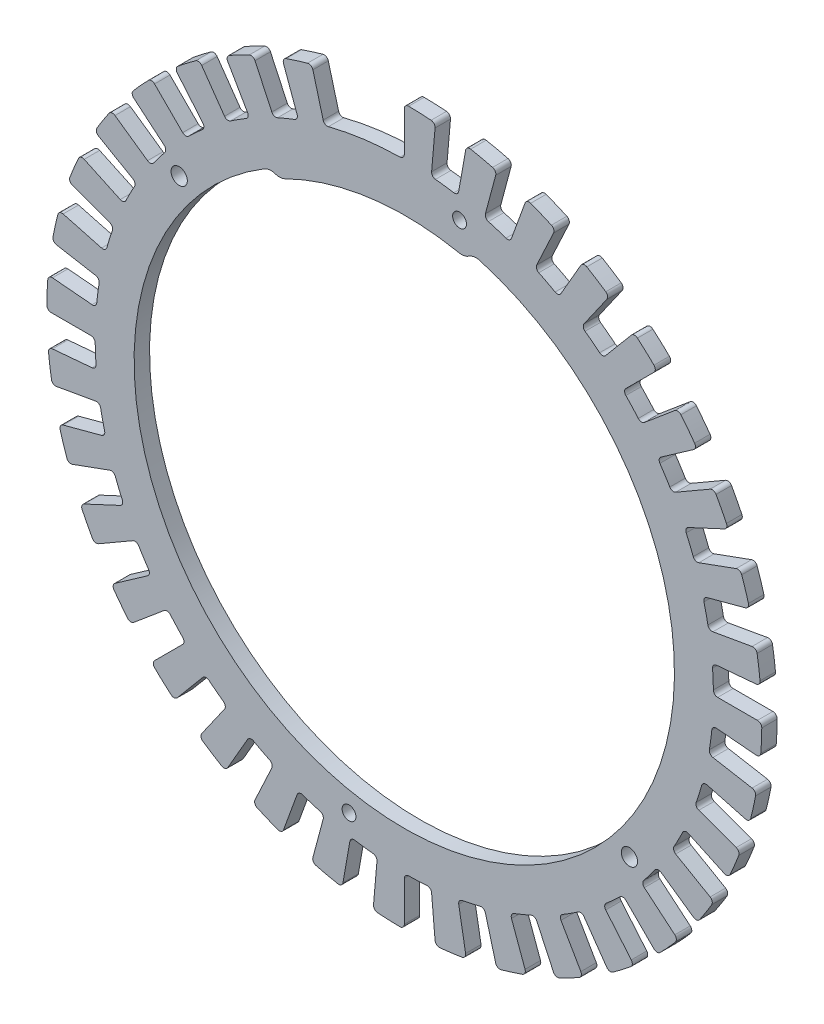
SolidWorks part; units mm, degrees
ref_plane "Front Plane" through (0, 0, 0) normal (0, 0, 1) x (1, 0, 0)
ref_plane "Top Plane" through (0, 0, 0) normal (0, 1, 0) x (1, 0, 0)
ref_plane "Right Plane" through (0, 0, 0) normal (1, 0, 0) x (0, 0, -1)
sketch "Sketch1" plane through (0, 0, 0) normal (0, 0, 1) x (1, 0, 0)
  line L0 (0, 82.7) -> (0, 71.5) construction
  line L1 (7.2078, 82.3853) -> (6.2316, 71.2279) construction
  line L2 (0, 71.5) -> (0, 0) construction
  line L3 (6.2316, 71.2279) -> (0, 0) construction
  line L4 (12.5883, 71.3918) -> (14.186, 80.4528) construction
  line L5 (12.5883, 71.3918) -> (0, 0) construction
  line L8 (0, 0) -> (12.7842, 65.769) construction
  line L12 (13.6428, 70.1863) -> (12.7842, 65.769) construction
  line L15 (12.7842, 65.769) -> (11.9256, 61.3517) construction
  line L18 (7.3144, 72.1301) -> (6.3182, 72.2172) construction
  line L21 (7.3144, 72.1301) -> (7.2135, 71.1352) construction
  line L24 (12.5883, 71.3918) -> (11.6035, 71.5654) construction
  line L27 (11.6035, 71.5654) -> (11.4434, 70.5783) construction
  line L30 (1.0122, 82.6938) -> (1, 81.6939) construction
  line L33 (1, 81.6939) -> (0, 81.6939) construction
  line L36 (7.1201, 81.383) -> (6.1239, 81.4702) construction
  line L39 (6.1239, 81.4702) -> (6.1989, 82.4674) construction
  line L42 (7.1201, 81.383) -> (6.3182, 72.2172)
  line L45 (0, 81.6939) -> (0, 72.4931)
  line L48 (0, 72.4931) -> (-1, 72.4931) construction
  line L51 (-1, 72.4931) -> (-0.9862, 71.4932) construction
  line L109 (0, -82.7) -> (0, -71.5) [skipped]
  line L111 (14.3607, 81.4436) -> (12.4158, 70.4138) [skipped]
  line L115 (41.35, 71.6203) -> (35.75, 61.9208) [skipped]
  line L117 (53.1585, 63.3519) -> (45.9593, 54.7722) [skipped]
  line L118 (-63.3519, -53.1585) -> (-54.7722, -45.9593) [skipped]
  line L119 (63.3519, 53.1585) -> (54.7722, 45.9593) [skipped]
  line L121 (71.6203, 41.35) -> (61.9208, 35.75) [skipped]
  line L123 (77.7126, 28.2851) -> (67.188, 24.4544) [skipped]
  line L125 (81.4436, 14.3607) -> (70.4138, 12.4158) [skipped]
  line L127 (82.7, 0) -> (71.5, 0) [skipped]
  line L129 (81.4436, -14.3607) -> (70.4138, -12.4158) [skipped]
  line L131 (77.7126, -28.2851) -> (67.188, -24.4544) [skipped]
  line L133 (71.6203, -41.35) -> (61.9208, -35.75) [skipped]
  line L135 (63.3519, -53.1585) -> (54.7722, -45.9593) [skipped]
  line L137 (53.1585, -63.3519) -> (45.9593, -54.7722) [skipped]
  line L139 (41.35, -71.6203) -> (35.75, -61.9208) [skipped]
  line L141 (28.2851, -77.7126) -> (24.4544, -67.188) [skipped]
  line L142 (14.3607, -81.4436) -> (12.4158, -70.4138) [skipped]
  line L143 (34.9505, 74.9517) -> (30.2172, 64.801) [skipped]
  line L144 (47.4348, 67.7439) -> (41.0107, 58.5694) [skipped]
  line L145 (58.4777, 58.4777) -> (50.5581, 50.5581) [skipped]
  line L146 (67.7439, 47.4348) -> (58.5694, 41.0107) [skipped]
  line L147 (74.9517, 34.9505) -> (64.801, 30.2172) [skipped]
  line L148 (79.8821, 21.4043) -> (69.0637, 18.5056) [skipped]
  line L149 (82.3853, 7.2078) -> (71.2279, 6.2316) [skipped]
  line L150 (82.3853, -7.2078) -> (71.2279, -6.2316) [skipped]
  line L151 (79.8821, -21.4043) -> (69.0637, -18.5056) [skipped]
  line L152 (74.9517, -34.9505) -> (64.801, -30.2172) [skipped]
  line L153 (67.7439, -47.4348) -> (58.5694, -41.0107) [skipped]
  line L154 (58.4777, -58.4777) -> (50.5581, -50.5581) [skipped]
  line L155 (47.4348, -67.7439) -> (41.0107, -58.5694) [skipped]
  line L156 (34.9505, -74.9517) -> (30.2172, -64.801) [skipped]
  line L157 (21.4043, -79.8821) -> (18.5056, -69.0637) [skipped]
  line L158 (7.2078, -82.3853) -> (6.2316, -71.2279) [skipped]
  line L159 (-7.2078, -82.3853) -> (-6.2316, -71.2279) [skipped]
  line L160 (-21.4043, -79.8821) -> (-18.5056, -69.0637) [skipped]
  line L161 (-34.9505, -74.9517) -> (-30.2172, -64.801) [skipped]
  line L162 (-47.4348, -67.7439) -> (-41.0107, -58.5694) [skipped]
  line L163 (-58.4777, -58.4777) -> (-50.5581, -50.5581) [skipped]
  line L164 (-67.7439, -47.4348) -> (-58.5694, -41.0107) [skipped]
  line L165 (-74.9517, -34.9505) -> (-64.801, -30.2172) [skipped]
  line L166 (-79.8821, -21.4043) -> (-69.0637, -18.5056) [skipped]
  line L167 (-82.3853, -7.2078) -> (-71.2279, -6.2316) [skipped]
  line L168 (-82.3853, 7.2078) -> (-71.2279, 6.2316) [skipped]
  line L169 (-79.8821, 21.4043) -> (-69.0637, 18.5056) [skipped]
  line L170 (-74.9517, 34.9505) -> (-64.801, 30.2172) [skipped]
  line L171 (-67.7439, 47.4348) -> (-58.5694, 41.0107) [skipped]
  line L172 (-58.4777, 58.4777) -> (-50.5581, 50.5581) [skipped]
  line L173 (-47.4348, 67.7439) -> (-41.0107, 58.5694) [skipped]
  line L174 (-34.9505, 74.9517) -> (-30.2172, 64.801) [skipped]
  line L175 (-21.4043, 79.8821) -> (-18.5056, 69.0637) [skipped]
  line L176 (21.4043, 79.8821) -> (18.5056, 69.0637) [skipped]
  line L209 (0, 0) -> (-12.7842, -65.769) construction
  line L210 (0, 0) -> (-52.0688, 42.1645) construction
  line L211 (0, 0) -> (52.0688, -42.1645) construction
  line L212 (14.186, 80.4528) -> (12.5883, 71.3918)
  line L213 (21.1439, 78.9102) -> (18.7626, 70.023)
  line L214 (27.941, 76.7671) -> (24.7941, 68.1212)
  line L215 (34.5253, 74.0398) -> (30.6369, 65.7011)
  line L216 (40.8469, 70.749) -> (36.2466, 62.7809)
  line L217 (46.8577, 66.9197) -> (41.5803, 59.3829)
  line L218 (52.5118, 62.5811) -> (46.5977, 55.5329)
  line L219 (57.7663, 57.7663) -> (51.2604, 51.2604)
  line L220 (62.5811, 52.5118) -> (55.5329, 46.5977)
  line L221 (66.9197, 46.8577) -> (59.3829, 41.5803)
  line L222 (70.749, 40.8469) -> (62.7809, 36.2466)
  line L223 (74.0398, 34.5253) -> (65.7011, 30.6369)
  line L224 (76.7671, 27.941) -> (68.1212, 24.7941)
  line L225 (78.9102, 21.1439) -> (70.023, 18.7626)
  line L226 (80.4528, 14.186) -> (71.3918, 12.5883)
  line L227 (81.383, 7.1201) -> (72.2172, 6.3182)
  line L228 (81.6939, 0) -> (72.4931, 0)
  line L229 (81.383, -7.1201) -> (72.2172, -6.3182)
  line L230 (80.4528, -14.186) -> (71.3918, -12.5883)
  line L231 (78.9102, -21.1439) -> (70.023, -18.7626)
  line L232 (76.7671, -27.941) -> (68.1212, -24.7941)
  line L233 (74.0398, -34.5253) -> (65.7011, -30.6369)
  line L234 (70.749, -40.8469) -> (62.7809, -36.2466)
  line L235 (66.9197, -46.8577) -> (59.3829, -41.5803)
  line L236 (62.5811, -52.5118) -> (55.5329, -46.5977)
  line L237 (57.7663, -57.7663) -> (51.2604, -51.2604)
  line L238 (52.5118, -62.5811) -> (46.5977, -55.5329)
  line L239 (46.8577, -66.9197) -> (41.5803, -59.3829)
  line L240 (40.8469, -70.749) -> (36.2466, -62.7809)
  line L241 (34.5253, -74.0398) -> (30.6369, -65.7011)
  line L242 (27.941, -76.7671) -> (24.7941, -68.1212)
  line L243 (21.1439, -78.9102) -> (18.7626, -70.023)
  line L244 (14.186, -80.4528) -> (12.5883, -71.3918)
  line L245 (7.1201, -81.383) -> (6.3182, -72.2172)
  line L246 (0, -81.6939) -> (0, -72.4931)
  line L247 (-7.1201, -81.383) -> (-6.3182, -72.2172)
  line L248 (-14.186, -80.4528) -> (-12.5883, -71.3918)
  line L249 (-21.1439, -78.9102) -> (-18.7626, -70.023)
  line L250 (-27.941, -76.7671) -> (-24.7941, -68.1212)
  line L251 (-34.5253, -74.0398) -> (-30.6369, -65.7011)
  line L252 (-40.8469, -70.749) -> (-36.2466, -62.7809)
  line L253 (-46.8577, -66.9197) -> (-41.5803, -59.3829)
  line L254 (-52.5118, -62.5811) -> (-46.5977, -55.5329)
  line L255 (-57.7663, -57.7663) -> (-51.2604, -51.2604)
  line L256 (-62.5811, -52.5118) -> (-55.5329, -46.5977)
  line L257 (-66.9197, -46.8577) -> (-59.3829, -41.5803)
  line L258 (-70.749, -40.8469) -> (-62.7809, -36.2466)
  line L259 (-74.0398, -34.5253) -> (-65.7011, -30.6369)
  line L260 (-76.7671, -27.941) -> (-68.1212, -24.7941)
  line L261 (-78.9102, -21.1439) -> (-70.023, -18.7626)
  line L262 (-80.4528, -14.186) -> (-71.3918, -12.5883)
  line L263 (-81.383, -7.1201) -> (-72.2172, -6.3182)
  line L264 (-81.6939, 0) -> (-72.4931, 0)
  line L265 (-81.383, 7.1201) -> (-72.2172, 6.3182)
  line L266 (-80.4528, 14.186) -> (-71.3918, 12.5883)
  line L267 (-78.9102, 21.1439) -> (-70.023, 18.7626)
  line L268 (-76.7671, 27.941) -> (-68.1212, 24.7941)
  line L269 (-74.0398, 34.5253) -> (-65.7011, 30.6369)
  line L270 (-70.749, 40.8469) -> (-62.7809, 36.2466)
  line L271 (-66.9197, 46.8577) -> (-59.3829, 41.5803)
  line L272 (-62.5811, 52.5118) -> (-55.5329, 46.5977)
  line L273 (-57.7663, 57.7663) -> (-51.2604, 51.2604)
  line L274 (-52.5118, 62.5811) -> (-46.5977, 55.5329)
  line L275 (-46.8577, 66.9197) -> (-41.5803, 59.3829)
  line L276 (-40.8469, 70.749) -> (-36.2466, 62.7809)
  line L277 (-34.5253, 74.0398) -> (-30.6369, 65.7011)
  line L278 (-27.941, 76.7671) -> (-24.7941, 68.1212)
  line L279 (-21.1439, 78.9102) -> (-18.7626, 70.023)
  line L280 (-0.9864, 71.4932) -> (-0.9862, 71.4932)
  line L281 (-32.3995, 53.4464) -> (-30.8444, 50.881) construction
  line L282 (-30.8444, 50.881) -> (-29.8635, 53.7161) construction
  line L283 (-29.8635, 53.7161) -> (-28.8826, 56.5512) construction
  line L284 (-28.8826, 56.5512) -> (-27.5181, 53.8795) construction
  line L285 (17.4626, 60.0109) -> (16.6244, 57.1304) construction
  line L286 (16.6244, 57.1304) -> (14.9432, 59.615) construction
  line L289 (13.262, 62.0997) -> (14.9432, 59.615) construction
  line L290 (-7.4414, 56.5227) -> (0, 0) construction
  line L291 (-27.5181, 53.8795) -> (-7.4414, 56.5227) construction
  line L292 (-7.4414, 56.5227) -> (12.6354, 59.1658) construction
  line L293 (13.262, 62.0997) -> (12.6354, 59.1658) construction
  line L294 (-28.4278, 55.6607) -> (13.0531, 61.1217) construction
  circle A0 centre (0, 0) radius 82.7 construction
  arc A1 (-32.3995, 53.4464) -> (17.4626, 60.0109) centre (0, 0) ccw
  circle A73 centre (12.7842, 65.769) radius 1.6
  circle A74 centre (12.7842, 65.769) radius 2.1 construction
  arc A78 (0, 71.5) -> (6.2316, 71.2279) centre (0, 0) cw construction
  arc A79 (6.3182, 72.2172) -> (7.2135, 71.1352) centre (7.3144, 72.1301) ccw
  arc A80 (11.4434, 70.5783) -> (12.5883, 71.3918) centre (11.6035, 71.5654) ccw construction
  arc A81 (7.1201, 81.383) -> (6.1989, 82.4674) centre (6.1239, 81.4702) ccw
  arc A82 (0, 81.6939) -> (1.0122, 82.6938) centre (1, 81.6939) cw
  arc A83 (6.5367, 74.7146) -> (13.0236, 73.8606) centre (0, 0) cw [skipped]
  arc A84 (7.2135, 71.1352) -> (11.4434, 70.5783) centre (0, 0) cw
  arc A85 (0, 82.7) -> (7.2078, 82.3853) centre (0, 0) cw [skipped]
  arc A86 (1.0122, 82.6938) -> (6.1989, 82.4674) centre (0, 0) cw
  arc A87 (28.2851, 77.7126) -> (34.9505, 74.9517) centre (0, 0) cw [skipped]
  arc A88 (31.6964, 67.9731) -> (37.5, 64.9519) centre (0, 0) cw [skipped]
  arc A89 (41.35, 71.6203) -> (47.4348, 67.7439) centre (0, 0) cw [skipped]
  arc A90 (43.0182, 61.4364) -> (48.2091, 57.4533) centre (0, 0) cw [skipped]
  arc A91 (53.1585, 63.3519) -> (58.4777, 58.4777) centre (0, 0) cw [skipped]
  arc A92 (53.033, 53.033) -> (57.4533, 48.2091) centre (0, 0) cw [skipped]
  arc A93 (63.3519, 53.1585) -> (67.7439, 47.4348) centre (0, 0) cw [skipped]
  arc A94 (61.4364, 43.0182) -> (64.9519, 37.5) centre (0, 0) cw [skipped]
  arc A95 (71.6203, 41.35) -> (74.9517, 34.9505) centre (0, 0) cw [skipped]
  arc A96 (67.9731, 31.6964) -> (70.4769, 25.6515) centre (0, 0) cw [skipped]
  arc A97 (77.7126, 28.2851) -> (79.8821, 21.4043) centre (0, 0) cw [skipped]
  arc A98 (72.4444, 19.4114) -> (73.8606, 13.0236) centre (0, 0) cw [skipped]
  arc A99 (81.4436, 14.3607) -> (82.3853, 7.2078) centre (0, 0) cw [skipped]
  arc A100 (74.7146, 6.5367) -> (75, 0) centre (0, 0) cw [skipped]
  arc A101 (82.7, 0) -> (82.3853, -7.2078) centre (0, 0) cw [skipped]
  arc A102 (74.7146, -6.5367) -> (73.8606, -13.0236) centre (0, 0) cw [skipped]
  arc A103 (81.4436, -14.3607) -> (79.8821, -21.4043) centre (0, 0) cw [skipped]
  arc A104 (72.4444, -19.4114) -> (70.4769, -25.6515) centre (0, 0) cw [skipped]
  arc A105 (77.7126, -28.2851) -> (74.9517, -34.9505) centre (0, 0) cw [skipped]
  arc A106 (67.9731, -31.6964) -> (64.9519, -37.5) centre (0, 0) cw [skipped]
  arc A107 (71.6203, -41.35) -> (67.7439, -47.4348) centre (0, 0) cw [skipped]
  arc A108 (61.4364, -43.0182) -> (57.4533, -48.2091) centre (0, 0) cw [skipped]
  arc A109 (63.3519, -53.1585) -> (58.4777, -58.4777) centre (0, 0) cw [skipped]
  arc A110 (53.033, -53.033) -> (48.2091, -57.4533) centre (0, 0) cw [skipped]
  arc A111 (53.1585, -63.3519) -> (47.4348, -67.7439) centre (0, 0) cw [skipped]
  arc A112 (43.0182, -61.4364) -> (37.5, -64.9519) centre (0, 0) cw [skipped]
  arc A113 (41.35, -71.6203) -> (34.9505, -74.9517) centre (0, 0) cw [skipped]
  arc A114 (31.6964, -67.9731) -> (25.6515, -70.4769) centre (0, 0) cw [skipped]
  arc A115 (28.2851, -77.7126) -> (21.4043, -79.8821) centre (0, 0) cw [skipped]
  arc A116 (19.4114, -72.4444) -> (13.0236, -73.8606) centre (0, 0) cw [skipped]
  arc A117 (14.3607, -81.4436) -> (7.2078, -82.3853) centre (0, 0) cw [skipped]
  arc A118 (6.5367, -74.7146) -> (0, -75) centre (0, 0) cw [skipped]
  arc A119 (0, -82.7) -> (-7.2078, -82.3853) centre (0, 0) cw [skipped]
  arc A120 (-6.5367, -74.7146) -> (-13.0236, -73.8606) centre (0, 0) cw [skipped]
  arc A121 (-14.3607, -81.4436) -> (-21.4043, -79.8821) centre (0, 0) cw [skipped]
  arc A122 (-28.2851, -77.7126) -> (-34.9505, -74.9517) centre (0, 0) cw [skipped]
  arc A123 (-19.4114, -72.4444) -> (-25.6515, -70.4769) centre (0, 0) cw [skipped]
  arc A124 (-31.6964, -67.9731) -> (-37.5, -64.9519) centre (0, 0) cw [skipped]
  arc A125 (-41.35, -71.6203) -> (-47.4348, -67.7439) centre (0, 0) cw [skipped]
  arc A126 (-43.0182, -61.4364) -> (-48.2091, -57.4533) centre (0, 0) cw [skipped]
  arc A127 (-53.1585, -63.3519) -> (-58.4777, -58.4777) centre (0, 0) cw [skipped]
  arc A128 (-53.033, -53.033) -> (-57.4533, -48.2091) centre (0, 0) cw [skipped]
  arc A129 (-63.3519, -53.1585) -> (-67.7439, -47.4348) centre (0, 0) cw [skipped]
  arc A130 (-61.4364, -43.0182) -> (-64.9519, -37.5) centre (0, 0) cw [skipped]
  arc A131 (-71.6203, -41.35) -> (-74.9517, -34.9505) centre (0, 0) cw [skipped]
  arc A132 (-67.9731, -31.6964) -> (-70.4769, -25.6515) centre (0, 0) cw [skipped]
  arc A133 (-77.7126, -28.2851) -> (-79.8821, -21.4043) centre (0, 0) cw [skipped]
  arc A134 (-72.4444, -19.4114) -> (-73.8606, -13.0236) centre (0, 0) cw [skipped]
  arc A135 (-81.4436, -14.3607) -> (-82.3853, -7.2078) centre (0, 0) cw [skipped]
  arc A136 (-74.7146, -6.5367) -> (-75, 0) centre (0, 0) cw [skipped]
  arc A137 (-82.7, 0) -> (-82.3853, 7.2078) centre (0, 0) cw [skipped]
  arc A138 (-74.7146, 6.5367) -> (-73.8606, 13.0236) centre (0, 0) cw [skipped]
  arc A139 (-81.4436, 14.3607) -> (-79.8821, 21.4043) centre (0, 0) cw [skipped]
  arc A140 (-72.4444, 19.4114) -> (-70.4769, 25.6515) centre (0, 0) cw [skipped]
  arc A141 (-77.7126, 28.2851) -> (-74.9517, 34.9505) centre (0, 0) cw [skipped]
  arc A142 (-67.9731, 31.6964) -> (-64.9519, 37.5) centre (0, 0) cw [skipped]
  arc A143 (-71.6203, 41.35) -> (-67.7439, 47.4348) centre (0, 0) cw [skipped]
  arc A144 (-61.4364, 43.0182) -> (-57.4533, 48.2091) centre (0, 0) cw [skipped]
  arc A145 (-63.3519, 53.1585) -> (-58.4777, 58.4777) centre (0, 0) cw [skipped]
  arc A146 (-53.033, 53.033) -> (-48.2091, 57.4533) centre (0, 0) cw [skipped]
  arc A147 (-53.1585, 63.3519) -> (-47.4348, 67.7439) centre (0, 0) cw [skipped]
  arc A148 (-43.0182, 61.4364) -> (-37.5, 64.9519) centre (0, 0) cw [skipped]
  arc A149 (-41.35, 71.6203) -> (-34.9505, 74.9517) centre (0, 0) cw [skipped]
  arc A150 (-31.6964, 67.9731) -> (-25.6515, 70.4769) centre (0, 0) cw [skipped]
  arc A151 (-28.2851, 77.7126) -> (-21.4043, 79.8821) centre (0, 0) cw [skipped]
  arc A152 (-19.4114, 72.4444) -> (-13.0236, 73.8606) centre (0, 0) cw [skipped]
  arc A153 (14.3607, 81.4436) -> (21.4043, 79.8821) centre (0, 0) cw [skipped]
  arc A154 (19.4114, 72.4444) -> (25.6515, 70.4769) centre (0, 0) cw [skipped]
  arc A155 (0, 72.4931) -> (-0.9862, 71.4932) centre (-1, 72.4931) cw
  circle A367 centre (-12.7842, -65.769) radius 1.6
  circle A368 centre (52.0688, -42.1645) radius 1.8812
  circle A369 centre (-52.0688, 42.1645) radius 1.8812
  circle A370 centre (0, 0) radius 71.5 construction
  arc A371 (12.5883, 71.3918) -> (11.4434, 70.5783) centre (11.6035, 71.5654) cw
  arc A372 (14.186, 80.4528) -> (15.3565, 81.2617) centre (15.1708, 80.2791) cw
  arc A373 (15.3565, 81.2617) -> (20.425, 80.1381) centre (0, 0) cw
  arc A374 (21.1439, 78.9102) -> (20.425, 80.1381) centre (20.178, 79.169) ccw
  arc A375 (18.7626, 70.023) -> (19.4564, 68.8019) centre (19.7285, 69.7641) ccw
  arc A376 (19.4564, 68.8019) -> (23.5254, 67.5189) centre (0, 0) cw
  arc A377 (24.7941, 68.1212) -> (23.5254, 67.5189) centre (23.8544, 68.4633) cw
  arc A378 (27.941, 76.7671) -> (29.2341, 77.3606) centre (28.8806, 76.4251) cw
  arc A379 (29.2341, 77.3606) -> (34.0305, 75.3738) centre (0, 0) cw
  arc A380 (34.5253, 74.0398) -> (34.0305, 75.3738) centre (33.619, 74.4624) ccw
  arc A381 (30.6369, 65.7011) -> (31.1081, 64.3781) centre (31.5432, 65.2784) ccw
  arc A382 (31.1081, 64.3781) -> (34.8925, 62.408) centre (0, 0) cw
  arc A384 (36.2466, 62.7809) -> (34.8925, 62.408) centre (35.3805, 63.2809) cw
  arc A385 (40.8469, 70.749) -> (42.2235, 71.1088) centre (41.713, 70.249) cw
  arc A386 (42.2235, 71.1088) -> (46.602, 68.3194) centre (0, 0) cw
  arc A387 (46.8577, 66.9197) -> (46.602, 68.3194) centre (46.0385, 67.4933) ccw
  arc A388 (41.5803, 59.3829) -> (41.8147, 57.9981) centre (42.3995, 58.8093) ccw
  arc A389 (41.8147, 57.9981) -> (45.1995, 55.4009) centre (0, 0) cw
  arc A390 (46.5977, 55.5329) -> (45.1995, 55.4009) centre (45.8316, 56.1757) cw
  arc A391 (52.5118, 62.5811) -> (53.93, 62.6965) centre (53.2779, 61.9384) cw
  arc A392 (53.93, 62.6965) -> (57.7576, 59.1891) centre (0, 0) cw
  arc A393 (57.7663, 57.7663) -> (57.7576, 59.1891) centre (57.0592, 58.4734) ccw
  arc A394 (51.2604, 51.2604) -> (51.2507, 49.856) centre (51.9675, 50.5533) ccw
  arc A395 (51.2507, 49.856) -> (54.133, 46.7104) centre (0, 0) cw
  arc A396 (55.5329, 46.5977) -> (54.133, 46.7104) centre (54.8902, 47.3637) cw
  arc A397 (62.5811, 52.5118) -> (63.9978, 52.3791) centre (63.2239, 51.7458) cw
  arc A398 (63.9978, 52.3791) -> (67.1582, 48.2604) centre (0, 0) cw
  arc A399 (66.9197, 46.8577) -> (67.1582, 48.2604) centre (66.3461, 47.6768) ccw
  arc A400 (59.3829, 41.5803) -> (59.1295, 40.199) centre (59.9565, 40.7612) ccw
  arc A401 (59.1295, 40.199) -> (61.4218, 36.6007) centre (0, 0) cw
  arc A402 (62.7809, 36.2466) -> (61.4218, 36.6007) centre (62.2809, 37.1126) cw
  arc A403 (70.749, 40.8469) -> (72.1211, 40.4703) centre (71.249, 39.9809) cw
  arc A404 (72.1211, 40.4703) -> (74.5182, 35.8653) centre (0, 0) cw
  arc A405 (74.0398, 34.5253) -> (74.5182, 35.8653) centre (73.6172, 35.4316) ccw
  arc A406 (65.7011, 30.6369) -> (65.2116, 29.3205) centre (66.1237, 29.7306) ccw
  arc A407 (65.2116, 29.3205) -> (66.8443, 25.3788) centre (0, 0) cw
  arc A408 (68.1212, 24.7941) -> (66.8443, 25.3788) centre (67.7792, 25.7338) cw
  arc A409 (76.7671, 27.941) -> (78.053, 27.3318) centre (77.1092, 27.0013) cw
  arc A410 (78.053, 27.3318) -> (79.6141, 22.3805) centre (0, 0) cw
  arc A411 (78.9102, 21.1439) -> (79.6141, 22.3805) centre (78.6514, 22.1099) ccw
  arc A412 (70.023, 18.7626) -> (69.3124, 17.5512) centre (70.2818, 17.7967) ccw
  arc A413 (69.3124, 17.5512) -> (70.2358, 13.3859) centre (0, 0) cw
  arc A414 (71.3918, 12.5883) -> (70.2358, 13.3859) centre (71.2181, 13.5731) cw
  arc A415 (80.4528, 14.186) -> (81.6133, 13.3628) centre (80.6264, 13.2012) cw
  arc A416 (81.6133, 13.3628) -> (82.2909, 8.2156) centre (0, 0) cw
  arc A417 (81.383, 7.1201) -> (82.2909, 8.2156) centre (81.2959, 8.1163) ccw
  arc A418 (72.2172, 6.3182) -> (71.3071, 5.2486) centre (72.3044, 5.322) ccw
  arc A419 (71.3071, 5.2486) -> (71.4932, 0.9862) centre (0, 0) cw
  arc A420 (72.4931, 0) -> (71.4932, 0.9862) centre (72.4931, 1) cw
  arc A421 (81.6939, 0) -> (82.6938, -1.0122) centre (81.6939, -1) cw
  arc A422 (82.6938, -1.0122) -> (82.4674, -6.1989) centre (0, 0) cw
  arc A423 (81.383, -7.1201) -> (82.4674, -6.1989) centre (81.4702, -6.1239) ccw
  arc A424 (72.2172, -6.3182) -> (71.1352, -7.2135) centre (72.1301, -7.3144) ccw
  arc A425 (71.1352, -7.2135) -> (70.5783, -11.4434) centre (0, 0) cw
  arc A426 (71.3918, -12.5883) -> (70.5783, -11.4434) centre (71.5654, -11.6035) cw
  arc A427 (80.4528, -14.186) -> (81.2617, -15.3565) centre (80.2791, -15.1708) cw
  arc A428 (81.2617, -15.3565) -> (80.1381, -20.425) centre (0, 0) cw
  arc A429 (78.9102, -21.1439) -> (80.1381, -20.425) centre (79.169, -20.178) ccw
  arc A430 (70.023, -18.7626) -> (68.8019, -19.4564) centre (69.7641, -19.7285) ccw
  arc A431 (68.8019, -19.4564) -> (67.5189, -23.5254) centre (0, 0) cw
  arc A432 (68.1212, -24.7941) -> (67.5189, -23.5254) centre (68.4633, -23.8544) cw
  arc A433 (76.7671, -27.941) -> (77.3606, -29.2341) centre (76.4251, -28.8806) cw
  arc A434 (77.3606, -29.2341) -> (75.3738, -34.0305) centre (0, 0) cw
  arc A435 (74.0398, -34.5253) -> (75.3738, -34.0305) centre (74.4624, -33.619) ccw
  arc A436 (65.7011, -30.6369) -> (64.3781, -31.1081) centre (65.2784, -31.5432) ccw
  arc A437 (64.3781, -31.1081) -> (62.408, -34.8925) centre (0, 0) cw
  arc A438 (62.7809, -36.2466) -> (62.408, -34.8925) centre (63.2809, -35.3805) cw
  arc A439 (70.749, -40.8469) -> (71.1088, -42.2235) centre (70.249, -41.713) cw
  arc A440 (71.1088, -42.2235) -> (68.3194, -46.602) centre (0, 0) cw
  arc A441 (66.9197, -46.8577) -> (68.3194, -46.602) centre (67.4933, -46.0385) ccw
  arc A442 (59.3829, -41.5803) -> (57.9981, -41.8147) centre (58.8093, -42.3995) ccw
  arc A443 (57.9981, -41.8147) -> (55.4009, -45.1995) centre (0, 0) cw
  arc A444 (55.5329, -46.5977) -> (55.4009, -45.1995) centre (56.1757, -45.8316) cw
  arc A445 (62.5811, -52.5118) -> (62.6965, -53.93) centre (61.9384, -53.2779) cw
  arc A446 (62.6965, -53.93) -> (59.1891, -57.7576) centre (0, 0) cw
  arc A447 (57.7663, -57.7663) -> (59.1891, -57.7576) centre (58.4734, -57.0592) ccw
  arc A448 (51.2604, -51.2604) -> (49.856, -51.2507) centre (50.5533, -51.9675) ccw
  arc A449 (49.856, -51.2507) -> (46.7104, -54.133) centre (0, 0) cw
  arc A450 (46.5977, -55.5329) -> (46.7104, -54.133) centre (47.3637, -54.8902) cw
  arc A451 (52.5118, -62.5811) -> (52.3791, -63.9978) centre (51.7458, -63.2239) cw
  arc A452 (52.3791, -63.9978) -> (48.2604, -67.1582) centre (0, 0) cw
  arc A453 (46.8577, -66.9197) -> (48.2604, -67.1582) centre (47.6768, -66.3461) ccw
  arc A454 (41.5803, -59.3829) -> (40.199, -59.1295) centre (40.7612, -59.9565) ccw
  arc A455 (40.199, -59.1295) -> (36.6007, -61.4218) centre (0, 0) cw
  arc A456 (36.2466, -62.7809) -> (36.6007, -61.4218) centre (37.1126, -62.2809) cw
  arc A457 (40.8469, -70.749) -> (40.4703, -72.1211) centre (39.9809, -71.249) cw
  arc A458 (40.4703, -72.1211) -> (35.8653, -74.5182) centre (0, 0) cw
  arc A459 (34.5253, -74.0398) -> (35.8653, -74.5182) centre (35.4316, -73.6172) ccw
  arc A460 (30.6369, -65.7011) -> (29.3205, -65.2116) centre (29.7306, -66.1237) ccw
  arc A461 (29.3205, -65.2116) -> (25.3788, -66.8443) centre (0, 0) cw
  arc A462 (24.7941, -68.1212) -> (25.3788, -66.8443) centre (25.7338, -67.7792) cw
  arc A463 (27.941, -76.7671) -> (27.3318, -78.053) centre (27.0013, -77.1092) cw
  arc A464 (27.3318, -78.053) -> (22.3805, -79.6141) centre (0, 0) cw
  arc A465 (21.1439, -78.9102) -> (22.3805, -79.6141) centre (22.1099, -78.6514) ccw
  arc A466 (18.7626, -70.023) -> (17.5512, -69.3124) centre (17.7967, -70.2818) ccw
  arc A467 (17.5512, -69.3124) -> (13.3859, -70.2358) centre (0, 0) cw
  arc A468 (12.5883, -71.3918) -> (13.3859, -70.2358) centre (13.5731, -71.2181) cw
  arc A469 (14.186, -80.4528) -> (13.3628, -81.6133) centre (13.2012, -80.6264) cw
  arc A470 (13.3628, -81.6133) -> (8.2156, -82.2909) centre (0, 0) cw
  arc A471 (7.1201, -81.383) -> (8.2156, -82.2909) centre (8.1163, -81.2959) ccw
  arc A472 (6.3182, -72.2172) -> (5.2486, -71.3071) centre (5.322, -72.3044) ccw
  arc A473 (5.2486, -71.3071) -> (0.9862, -71.4932) centre (0, 0) cw
  arc A474 (0, -72.4931) -> (0.9862, -71.4932) centre (1, -72.4931) cw
  arc A475 (0, -81.6939) -> (-1.0122, -82.6938) centre (-1, -81.6939) cw
  arc A476 (-1.0122, -82.6938) -> (-6.1989, -82.4674) centre (0, 0) cw
  arc A477 (-7.1201, -81.383) -> (-6.1989, -82.4674) centre (-6.1239, -81.4702) ccw
  arc A478 (-6.3182, -72.2172) -> (-7.2135, -71.1352) centre (-7.3144, -72.1301) ccw
  arc A479 (-7.2135, -71.1352) -> (-11.4434, -70.5783) centre (0, 0) cw
  arc A480 (-12.5883, -71.3918) -> (-11.4434, -70.5783) centre (-11.6035, -71.5654) cw
  arc A481 (-14.186, -80.4528) -> (-15.3565, -81.2617) centre (-15.1708, -80.2791) cw
  arc A482 (-15.3565, -81.2617) -> (-20.425, -80.1381) centre (0, 0) cw
  arc A483 (-21.1439, -78.9102) -> (-20.425, -80.1381) centre (-20.178, -79.169) ccw
  arc A484 (-18.7626, -70.023) -> (-19.4564, -68.8019) centre (-19.7285, -69.7641) ccw
  arc A485 (-19.4564, -68.8019) -> (-23.5254, -67.5189) centre (0, 0) cw
  arc A486 (-24.7941, -68.1212) -> (-23.5254, -67.5189) centre (-23.8544, -68.4633) cw
  arc A487 (-27.941, -76.7671) -> (-29.2341, -77.3606) centre (-28.8806, -76.4251) cw
  arc A488 (-29.2341, -77.3606) -> (-34.0305, -75.3738) centre (0, 0) cw
  arc A489 (-34.5253, -74.0398) -> (-34.0305, -75.3738) centre (-33.619, -74.4624) ccw
  arc A490 (-30.6369, -65.7011) -> (-31.1081, -64.3781) centre (-31.5432, -65.2784) ccw
  arc A491 (-31.1081, -64.3781) -> (-34.8925, -62.408) centre (0, 0) cw
  arc A492 (-36.2466, -62.7809) -> (-34.8925, -62.408) centre (-35.3805, -63.2809) cw
  arc A493 (-40.8469, -70.749) -> (-42.2235, -71.1088) centre (-41.713, -70.249) cw
  arc A494 (-42.2235, -71.1088) -> (-46.602, -68.3194) centre (0, 0) cw
  arc A495 (-46.8577, -66.9197) -> (-46.602, -68.3194) centre (-46.0385, -67.4933) ccw
  arc A496 (-41.5803, -59.3829) -> (-41.8147, -57.9981) centre (-42.3995, -58.8093) ccw
  arc A497 (-41.8147, -57.9981) -> (-45.1995, -55.4009) centre (0, 0) cw
  arc A498 (-46.5977, -55.5329) -> (-45.1995, -55.4009) centre (-45.8316, -56.1757) cw
  arc A499 (-52.5118, -62.5811) -> (-53.93, -62.6965) centre (-53.2779, -61.9384) cw
  arc A500 (-53.93, -62.6965) -> (-57.7576, -59.1891) centre (0, 0) cw
  arc A501 (-57.7663, -57.7663) -> (-57.7576, -59.1891) centre (-57.0592, -58.4734) ccw
  arc A502 (-51.2604, -51.2604) -> (-51.2507, -49.856) centre (-51.9675, -50.5533) ccw
  arc A503 (-51.2507, -49.856) -> (-54.133, -46.7104) centre (0, 0) cw
  arc A504 (-55.5329, -46.5977) -> (-54.133, -46.7104) centre (-54.8902, -47.3637) cw
  arc A505 (-62.5811, -52.5118) -> (-63.9978, -52.3791) centre (-63.2239, -51.7458) cw
  arc A506 (-63.9978, -52.3791) -> (-67.1582, -48.2604) centre (0, 0) cw
  arc A507 (-66.9197, -46.8577) -> (-67.1582, -48.2604) centre (-66.3461, -47.6768) ccw
  arc A508 (-59.3829, -41.5803) -> (-59.1295, -40.199) centre (-59.9565, -40.7612) ccw
  arc A509 (-59.1295, -40.199) -> (-61.4218, -36.6007) centre (0, 0) cw
  arc A510 (-62.7809, -36.2466) -> (-61.4218, -36.6007) centre (-62.2809, -37.1126) cw
  arc A511 (-70.749, -40.8469) -> (-72.1211, -40.4703) centre (-71.249, -39.9809) cw
  arc A512 (-72.1211, -40.4703) -> (-74.5182, -35.8653) centre (0, 0) cw
  arc A513 (-74.0398, -34.5253) -> (-74.5182, -35.8653) centre (-73.6172, -35.4316) ccw
  arc A514 (-65.7011, -30.6369) -> (-65.2116, -29.3205) centre (-66.1237, -29.7306) ccw
  arc A515 (-65.2116, -29.3205) -> (-66.8443, -25.3788) centre (0, 0) cw
  arc A516 (-68.1212, -24.7941) -> (-66.8443, -25.3788) centre (-67.7792, -25.7338) cw
  arc A517 (-76.7671, -27.941) -> (-78.053, -27.3318) centre (-77.1092, -27.0013) cw
  arc A518 (-78.053, -27.3318) -> (-79.6141, -22.3805) centre (0, 0) cw
  arc A519 (-78.9102, -21.1439) -> (-79.6141, -22.3805) centre (-78.6514, -22.1099) ccw
  arc A520 (-70.023, -18.7626) -> (-69.3124, -17.5512) centre (-70.2818, -17.7967) ccw
  arc A521 (-69.3124, -17.5512) -> (-70.2358, -13.3859) centre (0, 0) cw
  arc A522 (-71.3918, -12.5883) -> (-70.2358, -13.3859) centre (-71.2181, -13.5731) cw
  arc A523 (-80.4528, -14.186) -> (-81.6133, -13.3628) centre (-80.6264, -13.2012) cw
  arc A524 (-81.6133, -13.3628) -> (-82.2909, -8.2156) centre (0, 0) cw
  arc A525 (-81.383, -7.1201) -> (-82.2909, -8.2156) centre (-81.2959, -8.1163) ccw
  arc A526 (-72.2172, -6.3182) -> (-71.3071, -5.2486) centre (-72.3044, -5.322) ccw
  arc A527 (-71.3071, -5.2486) -> (-71.4932, -0.9862) centre (0, 0) cw
  arc A528 (-72.4931, 0) -> (-71.4932, -0.9862) centre (-72.4931, -1) cw
  arc A529 (-81.6939, 0) -> (-82.6938, 1.0122) centre (-81.6939, 1) cw
  arc A530 (-82.6938, 1.0122) -> (-82.4674, 6.1989) centre (0, 0) cw
  arc A531 (-81.383, 7.1201) -> (-82.4674, 6.1989) centre (-81.4702, 6.1239) ccw
  arc A532 (-72.2172, 6.3182) -> (-71.1352, 7.2135) centre (-72.1301, 7.3144) ccw
  arc A533 (-71.1352, 7.2135) -> (-70.5783, 11.4434) centre (0, 0) cw
  arc A534 (-71.3918, 12.5883) -> (-70.5783, 11.4434) centre (-71.5654, 11.6035) cw
  arc A535 (-80.4528, 14.186) -> (-81.2617, 15.3565) centre (-80.2791, 15.1708) cw
  arc A536 (-81.2617, 15.3565) -> (-80.1381, 20.425) centre (0, 0) cw
  arc A537 (-78.9102, 21.1439) -> (-80.1381, 20.425) centre (-79.169, 20.178) ccw
  arc A538 (-70.023, 18.7626) -> (-68.8019, 19.4564) centre (-69.7641, 19.7285) ccw
  arc A539 (-68.8019, 19.4564) -> (-67.5189, 23.5254) centre (0, 0) cw
  arc A540 (-68.1212, 24.7941) -> (-67.5189, 23.5254) centre (-68.4633, 23.8544) cw
  arc A541 (-76.7671, 27.941) -> (-77.3606, 29.2341) centre (-76.4251, 28.8806) cw
  arc A542 (-77.3606, 29.2341) -> (-75.3738, 34.0305) centre (0, 0) cw
  arc A543 (-74.0398, 34.5253) -> (-75.3738, 34.0305) centre (-74.4624, 33.619) ccw
  arc A544 (-65.7011, 30.6369) -> (-64.3781, 31.1081) centre (-65.2784, 31.5432) ccw
  arc A545 (-64.3781, 31.1081) -> (-62.408, 34.8925) centre (0, 0) cw
  arc A546 (-62.7809, 36.2466) -> (-62.408, 34.8925) centre (-63.2809, 35.3805) cw
  arc A547 (-70.749, 40.8469) -> (-71.1088, 42.2235) centre (-70.249, 41.713) cw
  arc A548 (-71.1088, 42.2235) -> (-68.3194, 46.602) centre (0, 0) cw
  arc A549 (-66.9197, 46.8577) -> (-68.3194, 46.602) centre (-67.4933, 46.0385) ccw
  arc A550 (-59.3829, 41.5803) -> (-57.9981, 41.8147) centre (-58.8093, 42.3995) ccw
  arc A551 (-57.9981, 41.8147) -> (-55.4009, 45.1995) centre (0, 0) cw
  arc A552 (-55.5329, 46.5977) -> (-55.4009, 45.1995) centre (-56.1757, 45.8316) cw
  arc A553 (-62.5811, 52.5118) -> (-62.6965, 53.93) centre (-61.9384, 53.2779) cw
  arc A554 (-62.6965, 53.93) -> (-59.1891, 57.7576) centre (0, 0) cw
  arc A555 (-57.7663, 57.7663) -> (-59.1891, 57.7576) centre (-58.4734, 57.0592) ccw
  arc A556 (-51.2604, 51.2604) -> (-49.856, 51.2507) centre (-50.5533, 51.9675) ccw
  arc A557 (-49.856, 51.2507) -> (-46.7104, 54.133) centre (0, 0) cw
  arc A558 (-46.5977, 55.5329) -> (-46.7104, 54.133) centre (-47.3637, 54.8902) cw
  arc A559 (-52.5118, 62.5811) -> (-52.3791, 63.9978) centre (-51.7458, 63.2239) cw
  arc A560 (-52.3791, 63.9978) -> (-48.2604, 67.1582) centre (0, 0) cw
  arc A561 (-46.8577, 66.9197) -> (-48.2604, 67.1582) centre (-47.6768, 66.3461) ccw
  arc A562 (-41.5803, 59.3829) -> (-40.199, 59.1295) centre (-40.7612, 59.9565) ccw
  arc A563 (-40.199, 59.1295) -> (-36.6007, 61.4218) centre (0, 0) cw
  arc A564 (-36.2466, 62.7809) -> (-36.6007, 61.4218) centre (-37.1126, 62.2809) cw
  arc A565 (-40.8469, 70.749) -> (-40.4703, 72.1211) centre (-39.9809, 71.249) cw
  arc A566 (-40.4703, 72.1211) -> (-35.8653, 74.5182) centre (0, 0) cw
  arc A567 (-34.5253, 74.0398) -> (-35.8653, 74.5182) centre (-35.4316, 73.6172) ccw
  arc A568 (-30.6369, 65.7011) -> (-29.3205, 65.2116) centre (-29.7306, 66.1237) ccw
  arc A569 (-29.3205, 65.2116) -> (-25.3788, 66.8443) centre (0, 0) cw
  arc A570 (-24.7941, 68.1212) -> (-25.3788, 66.8443) centre (-25.7338, 67.7792) cw
  arc A571 (-27.941, 76.7671) -> (-27.3318, 78.053) centre (-27.0013, 77.1092) cw
  arc A572 (-27.3318, 78.053) -> (-22.3805, 79.6141) centre (0, 0) cw
  arc A573 (-21.1439, 78.9102) -> (-22.3805, 79.6141) centre (-22.1099, 78.6514) ccw
  arc A574 (-18.7626, 70.023) -> (-17.5512, 69.3124) centre (-17.7967, 70.2818) ccw
  arc A575 (-17.5512, 69.3124) -> (-13.3859, 70.2358) centre (0, 0) cw
  arc A576 (-13.3859, 70.2358) -> (-0.9864, 71.4932) centre (0, 0) cw
  arc A577 (-29.8635, 53.7161) -> (-32.3995, 53.4464) centre (-30.8444, 50.881) ccw
  arc A578 (-29.8635, 53.7161) -> (-27.5181, 53.8795) centre (-28.8826, 56.5512) ccw
  arc A579 (17.4626, 60.0109) -> (14.9432, 59.615) centre (16.6244, 57.1304) ccw
  arc A580 (14.9432, 59.615) -> (12.6354, 59.1658) centre (13.262, 62.0997) cw
  circle A582 centre (0, 0) radius 62.5 construction
  arc A586 (-27.5181, 53.8795) -> (12.6354, 59.1658) centre (0.3099, -2.3542) cw
  circle A587 centre (-52.0688, 42.1645) radius 2.3812 construction
  circle A588 centre (52.0688, -42.1645) radius 2.3812 construction
  circle A589 centre (-12.7842, -65.769) radius 2.1 construction
  point P3 (-28.4278, 55.6607)
  point P29 (0, 0)
  point P133 (13.0531, 61.1217)
  point P252 (0, 0)
  point P703 (0, 0)
  point P728 (0, 0)
  point P763 (0, 0)
  dimension "D2" = 165.4
  dimension "D7" = 3.2
  dimension "D8" = 4.2
  dimension "D12" = 1
  dimension "D14" = 11.2
  dimension "D15" = 11.2
  dimension "D17" = 2
  dimension "D20" = 3.7625
  dimension "D21" = 3.2
  dimension "D22" = 3.7625
  dimension "D23" = 4.7625
  dimension "D3" = 5
  dimension "D4" = 67
  dimension "D6" = 11
  dimension "D10" = 62
  dimension "D11" = 5
  dimension "D9" = 4.5
  dimension "D16" = 7.5
  dimension "D18" = 40.5
  dimension "D19" = 3
  dimension "D5" = 35
  dimension "D13" = 35
extrude "Boss-Extrude1" add sketch "Sketch1" along normal blind 3.5719
